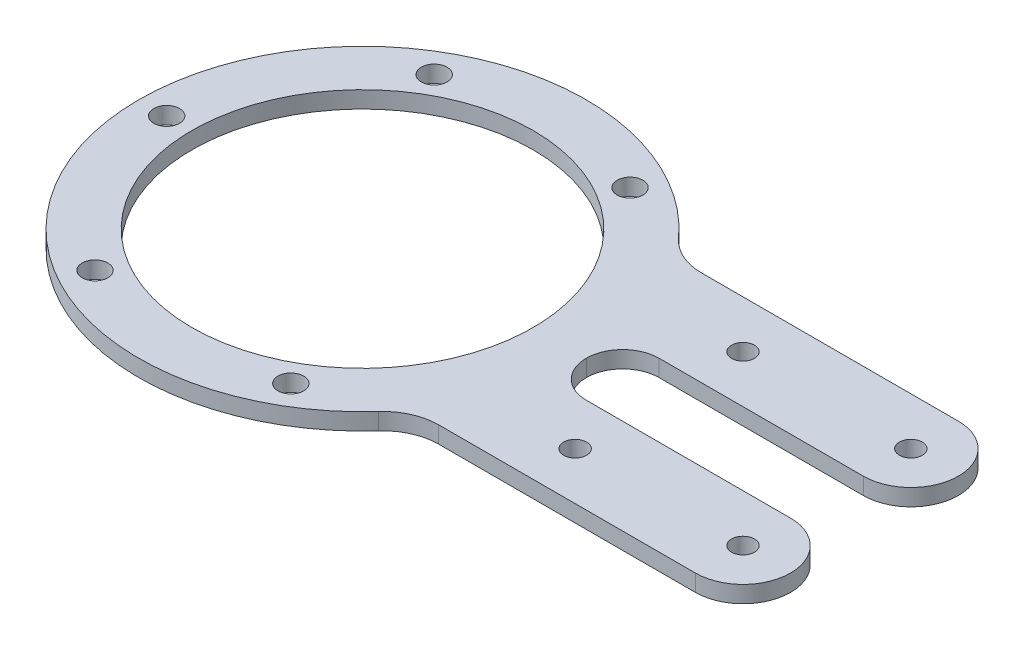
SolidWorks part; units mm, degrees
ref_plane "Front Plane" through (0, 0, 0) normal (0, 0, 1) x (1, 0, 0)
ref_plane "Top Plane" through (0, 0, 0) normal (0, 1, 0) x (1, 0, 0)
ref_plane "Right Plane" through (0, 0, 0) normal (1, 0, 0) x (0, 0, -1)
sketch "Sketch1" plane through (0, 0, 0) normal (0, 1, 0) x (1, 0, 0)
  circle A0 centre (0, 0) radius 40
  circle A1 centre (0, 0) radius 30.5
  dimension "D1" = 80
  dimension "D2" = 61
extrude "Boss-Extrude1" add sketch "Sketch1" along normal blind 3
sketch "Sketch2" plane through (0, 3, 0) normal (0, 1, 0) x (1, 0, 0)
  line L0 (100, 6.5) -> (39.4683, 6.5)
  line L1 (32.369, 23.5) -> (100, 23.5)
  line L4 (100, 23.5) -> (100, 6.5)
  line L5 (39.4683, -6.5) -> (100, -6.5)
  line L7 (32.369, -23.5) -> (100, -23.5)
  line L8 (100, -6.5) -> (100, -23.5)
  line L9 (32.7261, 23) -> (100, 23) construction
  line L11 (39.5474, 6) -> (100, 6) construction
  line L12 (100, 23) -> (100, 6) construction
  line L13 (39.5474, -6) -> (100, -6) construction
  line L15 (32.7261, -23) -> (100, -23) construction
  line L16 (100, -6) -> (100, -23) construction
  arc A0 (32.369, 23.5) -> (39.4683, 6.5) centre (0, 0) cw
  circle A1 centre (0, 0) radius 40 construction
  arc A2 (39.4683, -6.5) -> (32.369, -23.5) centre (0, 0) cw
  dimension "D1" = 100
  dimension "D2" = 17
  dimension "D3" = 12
  dimension "D4" = 0.5
  dimension "D5" = 0.5
  dimension "D6" = 0
extrude "Boss-Extrude2" add sketch "Sketch2" against normal up to surface (3 mm away) up to face at (0, 0, 40)
sketch "Sketch3" plane through (0, 3, 0) normal (0, 1, 0) x (1, 0, 0)
  line L0 (100, 6.5) -> (100, 23.5) construction
  line L1 (100, -23.5) -> (100, -6.5) construction
  line L2 (53, 15) -> (83, 15) construction
  line L3 (53, 15) -> (53, -15) construction
  line L4 (53, -15) -> (83, -15) construction
  line L5 (83, 15) -> (83, -15) construction
  circle A0 centre (53, 15) radius 2.05
  circle A1 centre (83, 15) radius 2.05
  circle A2 centre (53, -15) radius 2.05
  circle A3 centre (83, -15) radius 2.05
  circle A4 centre (0, 0) radius 30.5 construction
  point P10 (100, 15)
  point P14 (100, -15)
  dimension "D1" = 4.1
  dimension "D2" = 30
  dimension "D3" = 83
extrude "Cut-Extrude1" cut sketch "Sketch3" against normal through all
sketch "Sketch4" plane through (0, 3, 0) normal (0, 1, 0) x (1, 0, 0)
  circle A0 centre (0, 0) radius 35 construction
  circle A1 centre (-17.5, 30.3109) radius 2.3
  circle A2 centre (17.5, 30.3109) radius 2.3
  circle A4 centre (17.5, -30.3109) radius 2.3
  circle A5 centre (-17.5, -30.3109) radius 2.3
  circle A6 centre (-35, 0) radius 2.3
  circle A7 centre (35, 0) radius 2.3 [skipped]
  point P5 (0, 0)
  point P18 (0, 0)
  dimension "D1" = 70
  dimension "D2" = 4.6
  dimension "D3" = 6
extrude "Cut-Extrude2" cut sketch "Sketch4" against normal through all
sketch "Sketch6" plane through (0, 3, 0) normal (0, 1, 0) x (1, 0, 0)
  line L1 (100, 23.5) -> (83, 23.5)
  line L2 (100, 23.5) -> (100, 6.5)
  line L3 (100, 6.5) -> (83, 6.5)
  line L5 (100, -6.5) -> (83, -6.5)
  line L6 (100, -6.5) -> (100, -23.5)
  line L7 (100, -23.5) -> (83, -23.5)
  arc A0 (83, 6.5) -> (83, 23.5) centre (83, 15) ccw
  arc A1 (83, -23.5) -> (83, -6.5) centre (83, -15) ccw
extrude "Cut-Extrude3" cut sketch "Sketch6" against normal through all
fillet "Fillet1" radius 10 2 edges at (32.369, 1.5, -23.5) (32.369, 1.5, 23.5)
fillet "Fillet2" radius 6.5 2 edges at (39.4683, 1.5, 6.5) (39.4683, 1.5, -6.5)
